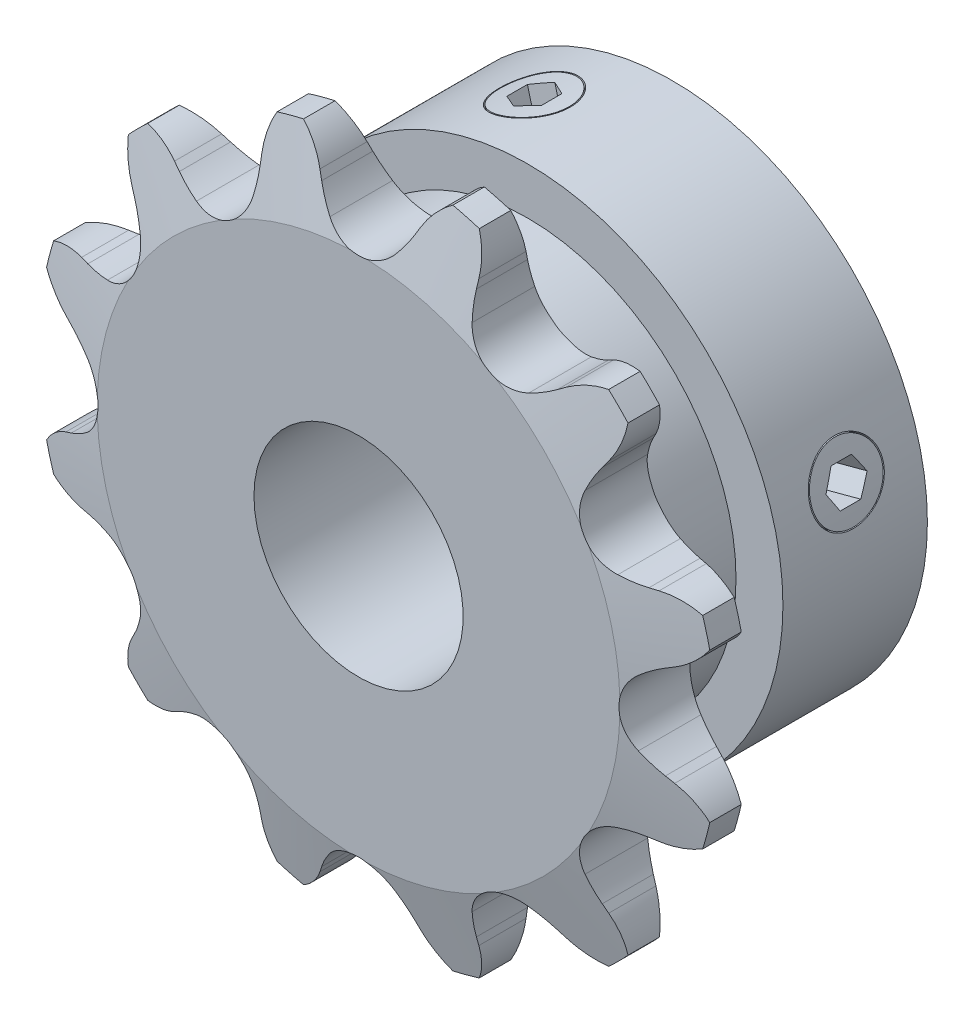
SolidWorks part; units mm, degrees
material "AISI 4130 Steel, annealed at 865C"
ref_plane "Front Plane" through (0, 0, 0) normal (0, 0, 1) x (1, 0, 0)
ref_plane "Top Plane" through (0, 0, 0) normal (0, 1, 0) x (1, 0, 0)
ref_plane "Right Plane" through (0, 0, 0) normal (1, 0, 0) x (0, 0, -1)
ref_axis "Axis1" through (0, 0, -88.99) along (0, 0, 1)
sketch "Sprocket-BaseSketch" plane through (0, 0, 0) normal (1, 0, 0) x (0, 0, -1)
  line L0 (2.1463, 0) -> (2.1463, 15.8689)
  line L1 (2.1463, 15.8689) -> (0.9557, 20.6314)
  line L2 (0.9557, 20.6314) -> (-0.9557, 20.6314)
  line L3 (-0.9557, 20.6314) -> (-2.1463, 15.8689)
  line L4 (-2.1463, 15.8689) -> (-2.1463, 0)
  line L5 (-2.1463, 0) -> (2.1463, 0)
  line L6 (8.5852, 0) -> (-2.6829, 0) construction
  dimension "Hub Surface" = 2.1463
  dimension "RightSide (1)" = 1.1906
  dimension "RightSide (2)" = 4.7625
  dimension "OD" = 20.6314
  dimension "LeftSide (1)" = 1.1906
  dimension "LeftSide (2)" = 4.7625
  dimension "Tooth Width" = 4.2926
revolve "35 (06C) ANSI (ISO) Chain Number, 1.449in P.D." add sketch "Sprocket-BaseSketch" angle 360 about L6
sketch "Tooth-Sketch" plane through (0, 0, 0) normal (0, 0, 1) x (1, 0, 0)
  line L0 (0, 0) -> (0, 24.5345) construction
  line L1 (2.8337, 18.0265) -> (3.0586, 18.4742)
  line L2 (-2.8337, 18.0265) -> (-3.0586, 18.4742)
  line L3 (0, 18.4009) -> (9.2004, 15.9356) construction
  line L4 (0, 18.4009) -> (-9.2004, 15.9356) construction
  arc A0 (-1.9847, 16.7356) -> (1.9847, 16.7356) centre (0, 18.4009) ccw
  arc A1 (1.9847, 16.7356) -> (2.8337, 18.0265) centre (-3.1132, 21.0132) ccw
  arc A2 (-1.9847, 16.7356) -> (-2.8337, 18.0265) centre (3.1132, 21.0132) cw
  arc A3 (3.0586, 18.4742) -> (6.8697, 20.8249) centre (6.8697, 16.5602) cw
  arc A4 (-3.0586, 18.4742) -> (-6.8697, 20.8249) centre (-6.8697, 16.5602) ccw
  arc A5 (6.8697, 20.8249) -> (-6.8697, 20.8249) centre (0, 0) ccw
extrude "Tooth-Cut, Number of teeth: 12" cut sketch "Tooth-Sketch" against normal through all and the other way through all
pattern_circular "Tooth Pattern, 12 / 12" count 12 every 30 about axis through (0, 0, -88.99) along (0, 0, 1) of "Tooth-Cut, Number of teeth: 12"
sketch "Sketch3" plane through (0, 0, 0) normal (1, 0, 0) x (0, 0, -1)
  line L0 (-14.7574, 0) -> (14.7574, 0) construction
  line L1 (2.1463, 0) -> (2.1463, 12.6304)
  line L2 (2.1463, 12.6304) -> (8.1344, 12.6304)
  line L3 (8.1344, 12.6304) -> (8.1344, 15.4788)
  line L4 (8.1344, 15.4788) -> (16.9037, 15.4788)
  line L5 (16.9037, 15.4788) -> (16.9037, 0)
  line L6 (16.9037, 0) -> (2.1463, 0)
  dimension "Hub Surface" = 2.1463
  dimension "Relief Diameter" = 12.6304
  dimension "Relief Width" = 5.9881
  dimension "Hub OD" = 15.4788
  dimension "Hub Width" = 14.7574
revolve "Hub-Revolve1" add sketch "Sketch3" angle 360 about L0
sketch "Sketch4" plane through (0, 0, 0) normal (1, 0, 0) x (0, 0, -1)
  line L0 (16.9037, 0) -> (-2.1463, 0) construction
  line L1 (16.9037, -15.4788) -> (16.9037, 15.4788) construction
  line L2 (-2.1463, 0.5096) -> (-2.1463, -0.5096) construction
ref_plane "Plane1" through (0, 0, 0) normal (-0.2588, 0.9659, 0) x (-0.9659, -0.2588, 0)
sketch "Sketch5" plane through (0, 0, -16.9037) normal (0, 0, -1) x (-1, 0, 0)
  circle A0 centre (0, 0) radius 6.35
  dimension "Bore Diameter " = 12.7
extrude "Cut-Extrude1" cut sketch "Sketch5" against normal through all
sketch "Sketch6" plane through (0, 0, -16.9037) normal (0, 0, -1) x (-1, 0, 0)
  line L0 (10.1205, -2.7118) -> (-10.1205, 2.7118) construction
  line L1 (0.0579, 6.3497) -> (3.1247, 5.528)
  line L2 (0.0579, 6.3497) -> (0.4688, 7.8831)
  line L3 (0.4688, 7.8831) -> (3.5356, 7.0614)
  line L4 (3.1247, 5.528) -> (3.5356, 7.0614)
  circle A0 centre (0, 0) radius 6.35 construction
  dimension "Keyway Dp " = 1.5875
  dimension "Keyway Wd " = 3.175
extrude "Cut-Extrude2" cut sketch "Sketch6" against normal through all
sketch "Sketch7" plane through (-2.0022, 7.4723, 0) normal (0.2588, -0.9659, 0) x (0.9659, 0.2588, 0)
  line L0 (0, -16.9037) -> (0, -8.1344) construction
  line L1 (12.6304, -8.1344) -> (-12.6304, -8.1344) construction
  line L3 (0, -12.519) -> (0, -14.6177) construction
  circle A0 centre (0, -12.519) radius 2.0987
  dimension "D1" = 2.286
extrude "Cut-Extrude3" cut sketch "Sketch7" against normal through all draft 1 draft outward yes
sketch "Sketch8" plane through (-2.0022, 7.4723, 0) normal (0.2588, -0.9659, 0) x (0.9659, 0.2588, 0)
  line L0 (-2.0987, -12.519) -> (-2.2309, -12.519) construction
  line L3 (-2.1648, -12.519) -> (-2.1648, -11.9789) construction
  circle A0 centre (0, -12.519) radius 2.1648
  circle A1 centre (0, -12.519) radius 2.0987 construction
  circle A2 centre (0, -12.519) radius 2.0987 construction
  spline S1 degree 3 poles (-1.8645, -13.7806) (-1.5716, -14.1114) (-1.4647, -14.2103) (-1.2334, -14.3861) (-1.1074, -14.4638) (-0.8444, -14.5919) (-0.7081, -14.6424) (-0.4257, -14.7167) (-0.2788, -14.7401) (0.1579, -14.7663) (0.455, -14.7252) (1.0047, -14.5347) (1.2629, -14.3834) (1.5892, -14.0935) (1.69, -13.9846) (1.8659, -13.7523) (1.9419, -13.6285) (2.0699, -13.3653) (2.1212, -13.2264) (2.1949, -12.9449) (2.2181, -12.8008) (2.2358, -12.506) (2.2301, -12.3602) (2.1906, -12.0717) (2.1563, -11.9274) (2.0608, -11.6507) (2.0001, -11.5186) (1.8531, -11.2666) (1.7661, -11.1464) (1.477, -10.8197) (1.2389, -10.6386) (0.8471, -10.4474) (0.7091, -10.3959) (0.425, -10.3212) (0.2812, -10.2982) (-0.0099, -10.2805) (-0.1587, -10.2861) (-0.448, -10.3258) (-0.5896, -10.3596) (-0.8665, -10.4553) (-1.0008, -10.5173) (-1.2517, -10.6642) (-1.37, -10.7499) (-1.59, -10.9451) (-1.6887, -11.052) (-1.8644, -11.2836) (-1.942, -11.4098) (-2.0698, -11.6727) (-2.1203, -11.809) (-2.1946, -12.0915) (-2.2181, -12.2384) (-2.2445, -12.6748) (-2.2039, -12.972) (-2.0145, -13.5222) (-1.8645, -13.7806) (-1.5716, -14.1114) (-1.4647, -14.2103) knots -0.0625 -0.0625 0 0 0.03125 0.03125 0.0625 0.0625 0.09375 0.09375 0.125 0.125 0.1875 0.1875 0.25 0.25 0.28125 0.28125 0.3125 0.3125 0.34375 0.34375 0.375 0.375 0.40625 0.40625 0.4375 0.4375 0.46875 0.46875 0.5 0.5 0.5625 0.5625 0.59375 0.59375 0.625 0.625 0.65625 0.65625 0.6875 0.6875 0.71875 0.71875 0.75 0.75 0.78125 0.78125 0.8125 0.8125 0.84375 0.84375 0.875 0.875 0.9375 0.9375 1 1 1.03125 1.03125 1.0625 only from (-1.6692, -14.0012) to (-1.6692, -14.0012) construction
extrude "Extrude1" add sketch "Sketch8" against normal up to surface (7.5908 mm away) up to face at (-2.7284, 15.2364, -10.7094)
sketch "Sketch9" plane through (-2.0022, 7.4723, 0) normal (0.2588, -0.9659, 0) x (0.9659, 0.2588, 0)
  line L0 (0, -12.519) -> (2.1648, -12.519) construction
  line L1 (0, -13.7689) -> (1.0824, -13.1439)
  line L2 (1.0824, -13.1439) -> (1.0824, -11.8941)
  line L3 (1.0824, -11.8941) -> (0, -11.2692)
  line L4 (0, -11.2692) -> (-1.0824, -11.8941)
  line L5 (-1.0824, -11.8941) -> (-1.0824, -13.1439)
  line L6 (-1.0824, -13.1439) -> (0, -13.7689)
  line L7 (1.0824, -12.519) -> (1.0824, -16.9037) construction
  line L8 (-15.4788, -16.9037) -> (15.4788, -16.9037) construction
  circle A0 centre (0, -12.519) radius 1.0824 construction
  circle A1 centre (0, -12.519) radius 2.1648 construction
extrude "Cut-Extrude4" cut sketch "Sketch9" against normal through all from offset 1.27 offset against normal yes
sketch "Sketch10" plane through (0, 0, -16.9037) normal (0, 0, -1) x (-1, 0, 0)
  line L0 (-19.9284, 5.3398) -> (19.9284, -5.3398)
  line L1 (10.1205, -2.7118) -> (-10.1205, 2.7118) construction
  line L2 (-9.2004, -15.9356) -> (0, -18.4009)
  line L3 (-20.3393, 3.8064) -> (19.5175, -6.8732)
  line L4 (-8.7896, -14.4022) -> (0.4109, -16.8675)
  circle A0 centre (0, 0) radius 20.6314
  circle A1 centre (0, 0) radius 6.35
  arc A2 (0.0579, 6.3497) -> (3.1247, 5.528) centre (0, 0) ccw construction
  arc A3 (-4.5324, 20.1274) -> (-6.1385, 19.697) centre (0, 0) ccw construction
  arc A4 (1.9847, -16.7356) -> (0.5096, -15.8607) centre (0, -18.4009) ccw construction
  arc A5 (-8.3717, -13.481) -> (-10.0865, -13.5011) centre (-9.2004, -15.9356) ccw construction
  dimension "D1" = 1.5875
  dimension "D2" = 1.5875
pattern_circular "CirPattern1" count 2 over 90 about axis through (0, 0, 2.1463) along (0, 0, -1) of "Cut-Extrude3", "Extrude1", "Cut-Extrude4"
sketch "Sketch11" plane through (0, 0, -16.9037) normal (0, 0, -1) x (-1, 0, 0)
  line L0 (0.4688, 7.8831) -> (0.0579, 6.3497) construction
  line L1 (3.5356, 7.0614) -> (0.4688, 7.8831) construction
  line L2 (3.1247, 5.528) -> (3.5356, 7.0614) construction
  line L3 (0.4688, 7.8831) -> (0.0579, 6.3497)
  line L4 (3.5356, 7.0614) -> (0.4688, 7.8831)
  line L5 (3.1247, 5.528) -> (3.5356, 7.0614)
  arc A0 (0.0579, 6.3497) -> (3.1247, 5.528) centre (0, 0) ccw construction
  arc A1 (3.1247, 5.528) -> (0.0579, 6.3497) centre (0, 0) ccw
extrude "Extrude2" add sketch "Sketch11" against normal up to vertex (19.05 mm away) up to point (-0.0579, 6.3497, 2.1463)
